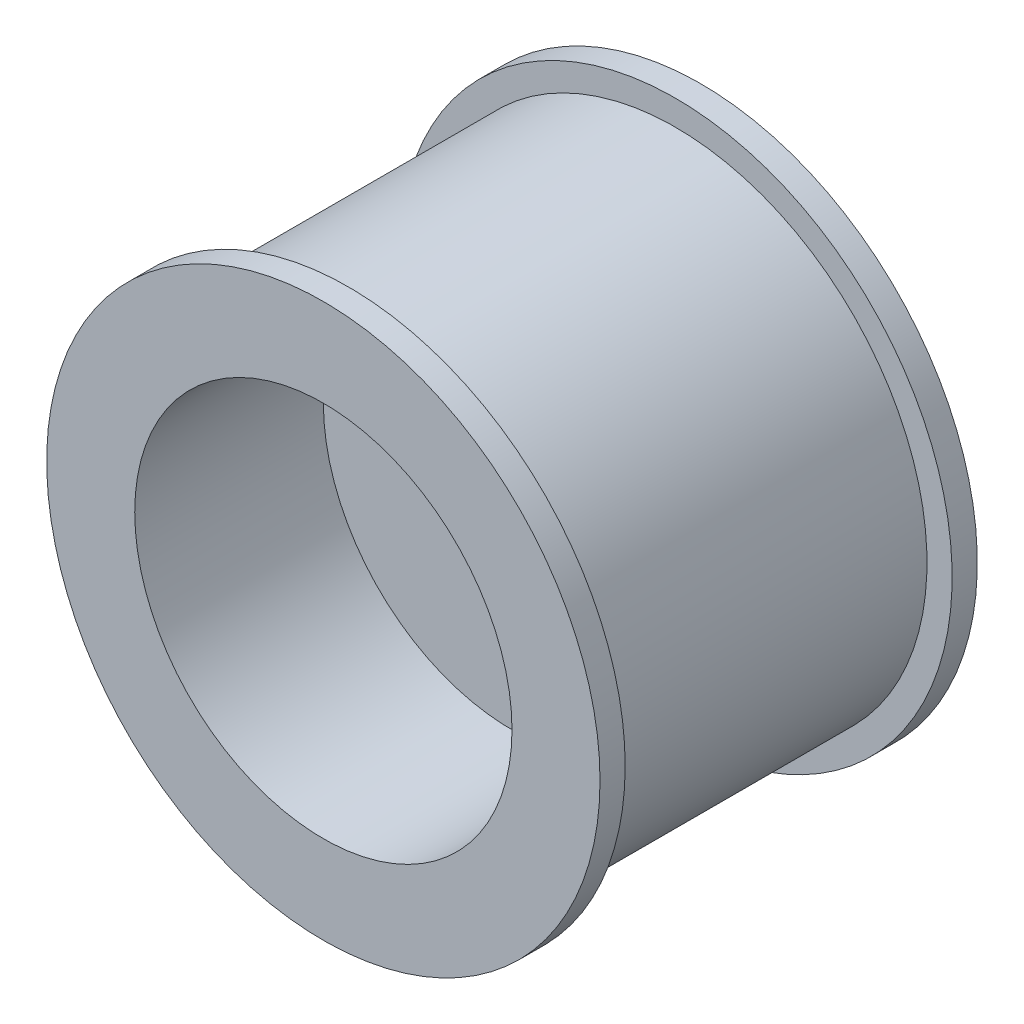
SolidWorks part; units mm, degrees
material "Aleación 1060"
ref_plane "Alzado" through (0, 0, 0) normal (0, 0, 1) x (1, 0, 0)
ref_plane "Planta" through (0, 0, 0) normal (0, 1, 0) x (1, 0, 0)
ref_plane "Vista lateral" through (0, 0, 0) normal (1, 0, 0) x (0, 0, -1)
sketch "Croquis2" plane through (0, 0, 0) normal (0, 0, 1) x (1, 0, 0)
  circle A1 centre (0, 0) radius 20
  dimension "D1" = 40
extrude "Saliente-Extruir1" add sketch "Croquis2" along normal blind 26
sketch "Croquis3" plane through (0, 0, 26) normal (0, 0, 1) x (1, 0, 0)
  circle A0 centre (0, 0) radius 22
  dimension "D1" = 44
extrude "Saliente-Extruir2" add sketch "Croquis3" along normal blind 2 from offset 0
sketch "Croquis4" plane through (0, 0, 0) normal (0, 0, -1) x (-1, 0, 0)
  circle A0 centre (0, 0) radius 22
  dimension "D1" = 44
extrude "Saliente-Extruir3" add sketch "Croquis4" along normal blind 2 contours A0
sketch "Croquis5" plane through (0, 0, 28) normal (0, 0, 1) x (1, 0, 0)
  circle A0 centre (0, 0) radius 15
  dimension "D1" = 30
extrude "Cortar-Extruir1" cut sketch "Croquis5" against normal blind 15
sketch "Croquis6" plane through (0, 0, 13) normal (0, 0, 1) x (1, 0, 0)
  circle A0 centre (0, 0) radius 3
  dimension "D1" = 6
extrude "Cortar-Extruir2" cut sketch "Croquis6" against normal through all
sketch "Croquis7" plane through (0, 0, -2) normal (0, 0, -1) x (-1, 0, 0)
  line L0 (0, 0) -> (0, 12.5) construction
  circle A0 centre (0, 12.5) radius 3
  circle A1 centre (0, 0) radius 12.5 construction
  circle A2 centre (0, 0) radius 3 construction
  circle A3 centre (10.8253, 6.25) radius 3
  circle A4 centre (10.8253, -6.25) radius 3
  circle A5 centre (0, -12.5) radius 3
  circle A6 centre (-10.8253, -6.25) radius 3
  circle A7 centre (-10.8253, 6.25) radius 3
  dimension "D1" = 6
  dimension "D2" = 12.5
  dimension "D3" = 6
extrude "Cortar-Extruir3" cut sketch "Croquis7" against normal blind 10 contours A0 | A3 | A4 | A5 | A6 | A7
